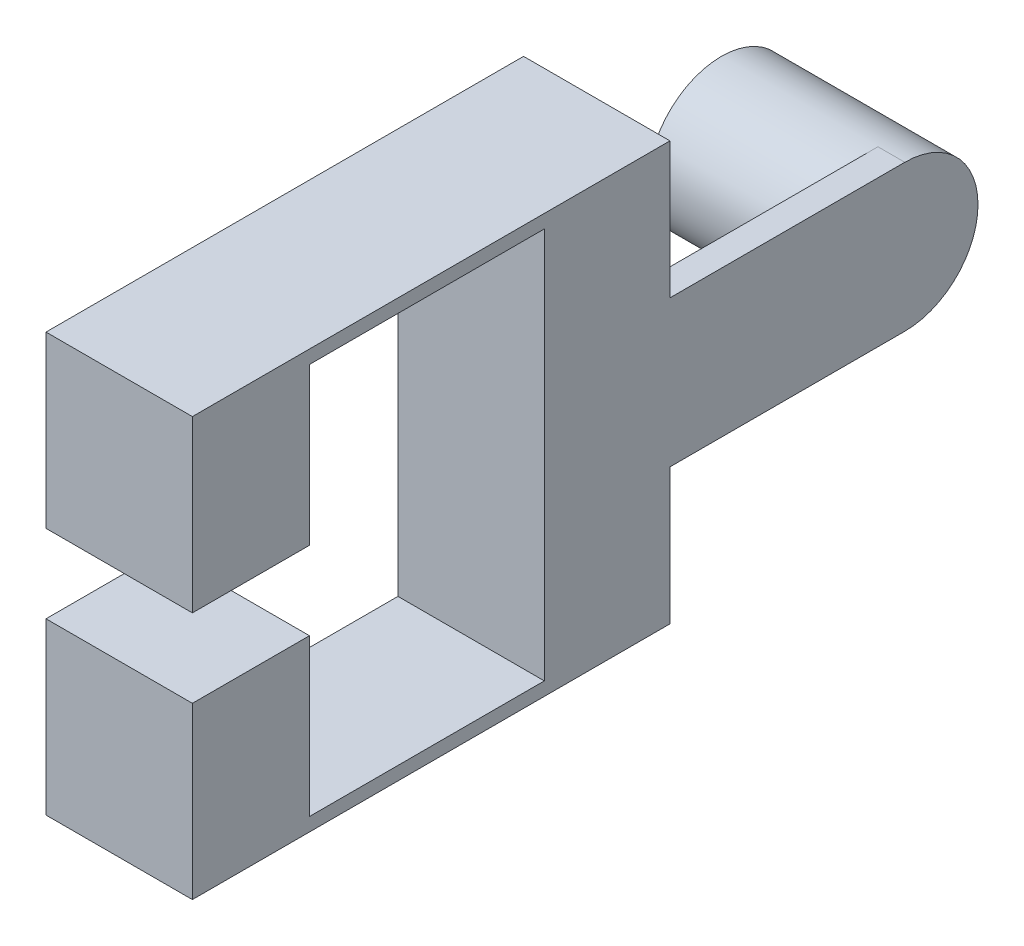
SolidWorks part; units mm, degrees
ref_plane "Front Plane" through (0, 0, 0) normal (1, 0, 0) x (0, 1, 0)
ref_plane "Top Plane" through (0, 0, 0) normal (0, 0, 1) x (0, 1, 0)
ref_plane "Right Plane" through (0, 0, 0) normal (0, 1, 0) x (-1, 0, 0)
sketch "Sketch1" plane through (0, 0, 0) normal (1, 0, 0) x (0, 1, 0)
  circle A0 centre (0, 0) radius 11.8736
  dimension "D1" = 23.7473
extrude "Boss-Extrude1" add sketch "Sketch1" along normal blind 25.4
sketch "Sketch2" plane through (25.4, 0, 0) normal (1, 0, 0) x (0, 1, 0)
  line L2 (-11.8736, 0) -> (-11.8736, 38.1)
  line L3 (-11.8736, 38.1) -> (11.8736, 38.1)
  line L4 (11.8736, 0) -> (11.8736, 38.1)
  circle A0 centre (0, 0) radius 11.8736 construction
  arc A1 (11.8736, 0) -> (-11.8736, 0) centre (0, 0) cw
  point P7 (11.8736, 38.1)
  point P9 (0, 0)
  point P10 (0, 0)
  point P11 (-11.8736, 0)
  point P12 (-11.8736, 0)
  dimension "D1" = 38.1
  dimension "D2" = 23.7473
extrude "Boss-Extrude2" add sketch "Sketch2" along normal blind 4.3594
sketch "Sketch3" plane through (0, 0, 38.1) normal (0, 0, 1) x (1, 0, 0)
  line L0 (6.0121, 31.75) -> (29.7594, 31.75)
  line L1 (6.0121, 31.75) -> (6.0121, -31.75)
  line L2 (29.7594, 31.75) -> (29.7594, -31.75)
  line L3 (6.0121, -31.75) -> (29.7594, -31.75)
  line L7 (29.7594, 11.8736) -> (29.7594, -11.8736) construction
  line L8 (29.7594, 0) -> (-39.2285, 0) construction
  point P1 (29.7594, 0)
  point P10 (0, 0)
  point P11 (0, 0)
  point P12 (0, 0)
  dimension "D2" = 23.7473
extrude "Boss-Extrude3" add sketch "Sketch3" along normal blind 20.3772
sketch "Sketch6" plane through (0, 31.75, 0) normal (0, 1, 0) x (-1, 0, 0)
  line L0 (-29.7594, 58.4772) -> (-6.0121, 58.4772) construction
  line L1 (-29.7594, 38.1) -> (-6.0121, 38.1)
  line L2 (-29.7594, 38.1) -> (-29.7594, 96.5772)
  line L3 (-29.7594, 96.5772) -> (-6.0121, 96.5772)
  line L4 (-6.0121, 38.1) -> (-6.0121, 96.5772)
  dimension "D1" = 23.7473
  dimension "D2" = 38.1
extrude "Boss-Extrude4" add sketch "Sketch6" along normal blind 2.1797 contours L3 L4 L1 L2
sketch "Sketch7" plane through (0, -31.75, 0) normal (0, -1, 0) x (1, 0, 0)
  line L0 (29.7594, 58.4772) -> (6.0121, 58.4772) construction
  line L1 (29.7594, 38.1) -> (6.0121, 38.1)
  line L2 (29.7594, 38.1) -> (29.7594, 96.5772)
  line L3 (29.7594, 96.5772) -> (6.0121, 96.5772)
  line L4 (6.0121, 38.1) -> (6.0121, 96.5772)
  dimension "D1" = 23.7473
  dimension "D2" = 38.1
extrude "Boss-Extrude5" add sketch "Sketch7" along normal blind 2.1797
sketch "Sketch8" plane through (0, 0, 96.5772) normal (0, 0, 1) x (1, 0, 0)
  line L1 (6.0121, 33.9297) -> (29.7594, 33.9297)
  line L2 (6.0121, 33.9297) -> (6.0121, 6.35)
  line L3 (6.0121, 6.35) -> (29.7594, 6.35)
  line L4 (29.7594, 33.9297) -> (29.7594, 6.35)
  line L5 (29.7594, -31.75) -> (29.7594, 31.75) construction
  line L6 (6.0121, -33.9297) -> (29.7594, -33.9297)
  line L7 (6.0121, -33.9297) -> (6.0121, -6.35)
  line L8 (6.0121, -6.35) -> (29.7594, -6.35)
  line L9 (29.7594, -33.9297) -> (29.7594, -6.35)
  dimension "D1" = 27.5797
  dimension "D2" = 27.5797
extrude "Boss-Extrude6" add sketch "Sketch8" along normal blind 18.9918
equation "\"F\"= 800"
equation "\"P\" = 2 * \"F\""
equation "\"n\"= 4"
equation "\"Sy\"= 39885"
equation "\"Emod\"= 10007604"
equation "\"dmax\"= 0.005"
equation "\"l_A\"= 1"
equation "\"Z_A\"= \"n\" * \"P\" * \"l_A\" / ( 2 * \"Sy\" )"
equation "\"r_A\"= ( 4 * \"Z_A\" / pi ) ^ ( 1 / 3 )"
equation "\"d_A\"= 2 * \"r_A\""
equation "\"w\"= \"d_A\""
equation "\"L_B\"= 1.5"
equation "\"A_B\"= \"n\" * \"P\" / \"Sy\""
equation "\"t_B\"= \"A_B\" / \"w\""
equation "\"C\" = 2 * 1.0 + 0.5"
equation "\"M_C\"= \"P\" * \"C\" / 4"
equation "\"Z_C\"= \"n\" * \"M_C\" / \"Sy\""
equation "\"t_C\"= ( 6 * \"Z_C\" / \"w\" ) ^ ( 1 / 2 )"
equation "\"D\" = 1.5"
equation "\"P_D\"= \"P\" / 2"
equation "\"A_D\"= \"n\" * \"P_D\" / \"Sy\""
equation "\"t_D\"= \"A_D\" / \"w\""
equation "\"E_len\"= ( \"C\" - 0.5 ) / 2 + \"t_D\""
equation "\"M_E\"= \"P_D\" * \"E_len\""
equation "\"Z_E\"= \"n\" * \"M_E\" / \"Sy\""
equation "\"t_E\"= ( 6 * \"Z_E\" / \"w\" ) ^ ( 1 / 2 )"
equation "\"D1@Sketch1\"=\"r_A\" *2"
equation "\"D1@Boss-Extrude1\"=\"l_A\""
equation "\"D1@Sketch2\"=\"L_B\""
equation "\"D2@Sketch2\"=\"w\""
equation "\"D1@Boss-Extrude2\"=\"t_B\""
equation "\"D1@Sketch3\"=\"C\""
equation "\"D1@Boss-Extrude3\"=\"t_C\""
equation "\"D2@Sketch3\"=\"w\""
equation "\"D1@Sketch6\"=\"w\""
equation "\"D2@Sketch6\"=\"D\""
equation "\"D1@Boss-Extrude4\"=\"t_D\""
equation "\"D1@Sketch7\"=\"w\""
equation "\"D2@Sketch7\"=\"D\""
equation "\"D1@Boss-Extrude5\"=\"t_D\""
equation "\"D1@Sketch8\"=\"E_len\""
equation "\"D2@Sketch8\"=\"E_len\""
equation "\"D1@Boss-Extrude6\"=\"t_E\""
